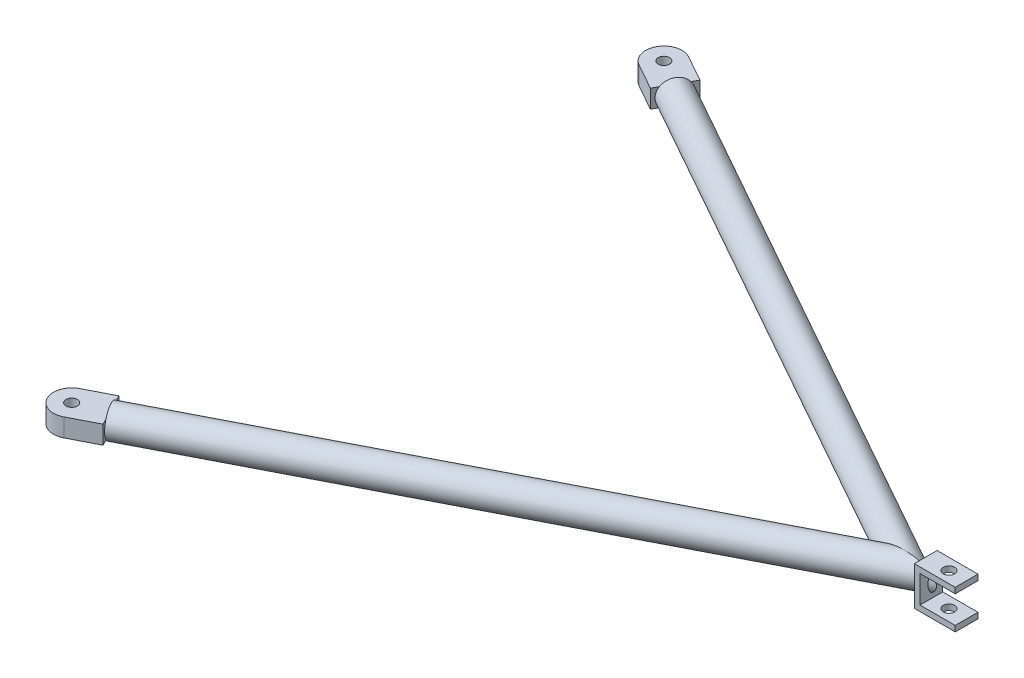
SolidWorks part; units mm, degrees
ref_plane "Front Plane" through (0, 0, 0) normal (0, 0, 1) x (1, 0, 0)
ref_plane "Top Plane" through (0, 0, 0) normal (0, 1, 0) x (1, 0, 0)
ref_plane "Right Plane" through (0, 0, 0) normal (1, 0, 0) x (0, 0, -1)
sketch "Sketch1" plane through (0, 0, 0) normal (0, 1, 0) x (1, 0, 0)
  line L0 (-307.2634, -157.8543) -> (0, 0)
  line L1 (0, 0) -> (-307.2634, 172.3457)
  line L2 (-307.2634, 172.3457) -> (-307.2634, -157.8543) construction
  dimension "D1" = 345.44
  dimension "D2" = 352.298
  dimension "D3" = 330.2
ref_plane "Plane1" through (-307.2634, 0, 157.8543) normal (0.8895, 0, -0.457) x (-0.457, 0, -0.8895)
sketch "Sketch2" plane through (-307.2634, 0, 157.8543) normal (0.8895, 0, -0.457) x (-0.457, 0, -0.8895)
  circle A0 centre (0, 0) radius 8.255
  dimension "D1" = 16.51
sweep "Sweep1" add profiles "Sketch2" path "Sketch1"
sketch "Sketch3" plane through (0, 0, 0) normal (0, 0, 1) x (1, 0, 0)
  line L0 (33.9318, 10.795) -> (11.0934, 10.795)
  line L1 (11.0934, 10.795) -> (11.0934, -10.795)
  line L2 (11.0934, -10.795) -> (33.9318, -10.795)
  line L3 (33.9318, -10.795) -> (33.9318, -7.62)
  line L4 (33.9318, -7.62) -> (14.2684, -7.62)
  line L5 (14.2684, -7.62) -> (14.2684, 7.62)
  line L6 (14.2684, 7.62) -> (33.9318, 7.62)
  line L7 (33.9318, 7.62) -> (33.9318, 10.795)
  line L8 (17.4434, 0) -> (-17.4435, 0) construction
  ellipse E0 centre (0, 0) end of major axis (17.4434, 0) minor radius 8.255 construction
  ellipse E1 centre (0, 0) end of major axis (17.4434, 0) minor radius 8.255 construction
  point P21 (11.0934, 0)
  dimension "D1" = 3.175
  dimension "D2" = 15.24
  dimension "D3" = 3.175
  dimension "D4" = 6.35
extrude "Boss-Extrude1" add sketch "Sketch3" along normal blind 6.35 and the other way blind 6.35
sketch "Sketch4" plane through (-307.2634, 0, 157.8543) normal (-0.8895, 0, 0.457) x (0.457, 0, 0.8895)
  line L1 (-10.16, 5.08) -> (10.16, 5.08)
  line L2 (-10.16, 5.08) -> (-10.16, -5.08)
  line L3 (-10.16, -5.08) -> (10.16, -5.08)
  line L4 (10.16, 5.08) -> (10.16, -5.08)
  line L5 (-10.16, 5.08) -> (10.16, -5.08) construction
  line L6 (-10.16, -5.08) -> (10.16, 5.08) construction
  circle A1 centre (0, 0) radius 8.255
  circle A2 centre (0, 0) radius 8.255 construction
  dimension "D2" = 20.32
  dimension "D3" = 10.16
  dimension "D1" = 0
extrude "Boss-Extrude2" add sketch "Sketch4" along normal blind 10.16 and the other way blind 16.256
sketch "Sketch5" plane through (-307.2634, 0, -172.3457) normal (-0.8722, 0, -0.4892) x (-0.4892, 0, 0.8722)
  line L1 (-10.16, 5.08) -> (10.16, 5.08)
  line L2 (-10.16, 5.08) -> (-10.16, -5.08)
  line L3 (-10.16, -5.08) -> (10.16, -5.08)
  line L4 (10.16, 5.08) -> (10.16, -5.08)
  line L5 (-10.16, 5.08) -> (10.16, -5.08) construction
  line L6 (-10.16, -5.08) -> (10.16, 5.08) construction
  point P0 (0, 0)
  dimension "D1" = 20.32
  dimension "D2" = 10.16
extrude "Boss-Extrude3" add sketch "Sketch5" along normal blind 10.16 and the other way blind 16.51
sketch "Sketch6" plane through (0, 5.08, 0) normal (0, 1, 0) x (1, 0, 0)
  line L0 (-287.8936, 173.1302) -> (-311.1544, 186.1773) construction
  line L1 (-297.8343, 155.4077) -> (-321.095, 168.4548) construction
  line L2 (-321.095, 168.4548) -> (-311.1544, 186.1773) construction
  line L3 (-312.2338, 163.4845) -> (-321.095, 168.4548)
  line L4 (-321.095, 168.4548) -> (-316.1247, 177.3161)
  arc A0 (-316.1247, 177.3161) -> (-312.2338, 163.4845) centre (-307.2634, 172.3457) ccw
extrude "Cut-Extrude1" cut sketch "Sketch6" against normal through all
ref_plane "Plane2" through (0, 0, 0) normal (-0.4892, 0, 0.8722) x (0.8722, 0, 0.4892)
ref_plane "Plane3" through (0, 0, 0) normal (0.457, 0, 0.8895) x (0.8895, 0, -0.457)
mirror "Mirror1" about plane through (0, 0, 0) normal (-0.4892, 0, 0.8722) of "Cut-Extrude1"
sketch "Sketch7" plane through (0, 5.08, 0) normal (0, 1, 0) x (1, 0, 0)
  line L0 (-288.1612, -159.463) -> (-311.6578, -171.5342) construction
  line L1 (-297.4468, -141.3887) -> (-320.9434, -153.4599) construction
  line L2 (-311.6578, -171.5342) -> (-320.9434, -153.4599) construction
  line L3 (-302.6207, -166.8914) -> (-311.6578, -171.5342)
  line L4 (-311.6578, -171.5342) -> (-316.3006, -162.497)
  arc A0 (-302.6207, -166.8914) -> (-316.3006, -162.497) centre (-307.2634, -157.8543) cw
extrude "Cut-Extrude2" cut sketch "Sketch7" against normal through all
mirror "Mirror2" about plane through (0, 0, 0) normal (0.457, 0, 0.8895) of "Cut-Extrude2"
sketch "Sketch8" plane through (-307.2634, 0, 157.8543) normal (-0.8895, 0, 0.457) x (0.457, 0, 0.8895)
  line L0 (6.5068, -5.08) -> (-6.5068, -5.08) construction
  line L1 (-6.5068, 5.08) -> (6.5068, 5.08) construction
  line L2 (6.5068, -5.08) -> (-6.5068, -5.08)
  line L3 (-6.5068, 5.08) -> (6.5068, 5.08)
  arc A0 (-6.5068, -5.08) -> (6.5068, -5.08) centre (0, 0) ccw construction
  arc A1 (6.5068, 5.08) -> (-6.5068, 5.08) centre (0, 0) ccw construction
  arc A2 (-6.5068, -5.08) -> (6.5068, -5.08) centre (0, 0) ccw
  arc A3 (6.5068, 5.08) -> (-6.5068, 5.08) centre (0, 0) ccw
extrude "Cut-Extrude3" cut sketch "Sketch8" against normal up to surface (16.256 mm away) up to face at (-288.7962, 0, 158.227)
sketch "Sketch9" plane through (-307.2634, 0, -172.3457) normal (-0.8722, 0, -0.4892) x (-0.4892, 0, 0.8722)
  line L0 (6.5068, -5.08) -> (-6.5068, -5.08) construction
  line L1 (-6.5068, 5.08) -> (6.5068, 5.08) construction
  line L2 (6.5068, -5.08) -> (-6.5068, -5.08)
  line L3 (-6.5068, 5.08) -> (6.5068, 5.08)
  arc A0 (-6.5068, -5.08) -> (6.5068, -5.08) centre (0, 0) ccw construction
  arc A1 (6.5068, 5.08) -> (-6.5068, 5.08) centre (0, 0) ccw construction
  arc A2 (-6.5068, -5.08) -> (6.5068, -5.08) centre (0, 0) ccw
  arc A3 (6.5068, 5.08) -> (-6.5068, 5.08) centre (0, 0) ccw
extrude "Cut-Extrude4" cut sketch "Sketch9" against normal up to surface (16.51 mm away) up to face at (-297.1545, 0, -156.6197)
sketch "Sketch10" plane through (0, 5.08, 0) normal (0, 1, 0) x (1, 0, 0)
  point P0 (-307.2634, 172.3457)
  point P1 (-307.2634, -157.8543)
  point P3 (0, 0)
hole_wizard "E (0.25) Diameter Hole1" positions "3DSketch1" profile "Sketch11" hole size "E" standard "ANSI Inch"
sketch3d "3DSketch1"
  point P0 (-307.2634, 5.08, -172.3457)
  point P3 (-307.2634, 5.08, 157.8543)
sketch "Sketch11" plane through (-307.2634, 5.08, -172.3457) normal (1, 0, 0) x (0, 0, 1)
  line L0 (0, 0) -> (0, 20.9577)
  line L1 (0, 20.9577) -> (3.175, 19.05)
  line L2 (3.175, 19.05) -> (3.175, 0)
  line L5 (3.175, 0) -> (0, 0)
  line L10 (0, 20.9577) -> (-3.175, 19.05) construction
  line L11 (0, -6.35) -> (0, 107.95) construction
  dimension "Hole Dia." = 6.35
  dimension "Hole Depth" = 19.05
  dimension "Drill Angle" = 118
sketch "Sketch13" plane through (0, -7.62, 0) normal (0, 1, 0) x (1, 0, 0)
  line L0 (14.2684, 6.35) -> (33.9318, -6.35) construction
  line L1 (33.9318, 6.35) -> (14.2684, -6.35) construction
  line L4 (14.2684, 6.35) -> (14.2684, -6.35)
  line L5 (14.2684, -6.35) -> (33.9318, -6.35)
  line L6 (33.9318, -6.35) -> (33.9318, 6.35)
  line L7 (33.9318, 6.35) -> (14.2684, 6.35)
  line L8 (14.2684, 6.35) -> (14.2684, -6.35) construction
  line L9 (14.2684, -6.35) -> (33.9318, -6.35) construction
  line L10 (33.9318, -6.35) -> (33.9318, 6.35) construction
  line L11 (33.9318, 6.35) -> (14.2684, 6.35) construction
  circle A0 centre (24.1001, 0) radius 3.175
  dimension "D2" = 6.35
  dimension "D1" = 0
extrude "Cut-Extrude5" cut sketch "Sketch13" against normal through all both and the other way through all
ref_point "Point1"
ref_point "Point2"
sketch3d "3DSketch2"
  line L0 (24.1001, 10.795, 0) -> (24.1001, -10.795, 0)
  circle A0 centre (24.1001, -10.795, 0) radius 3.175 construction
  circle A1 centre (24.1001, 10.795, 0) radius 3.175 construction
  circle A2 centre (24.1001, -10.795, 0) radius 3.175
  circle A3 centre (24.1001, 10.795, 0) radius 3.175
  point P2 (24.1001, -7.62, 0)
  point P5 (24.1001, 13.97, 0)
  point P7 (24.1001, -7.62, 0)
  point P9 (24.1001, 13.97, 0)
  point P10 (24.1001, 0, 0)
ref_point "JOINT"
